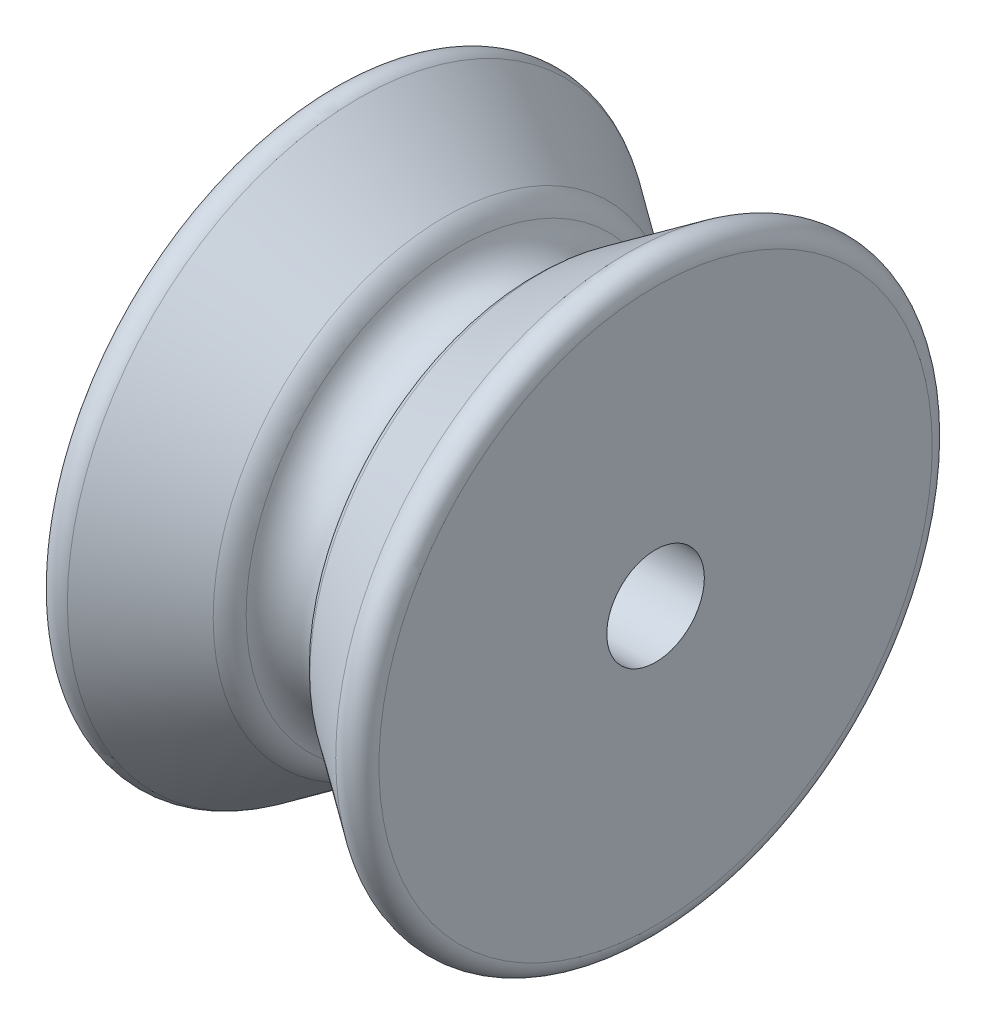
SolidWorks part; units mm, degrees
ref_plane "Front Plane" through (0, 0, 0) normal (0, 0, 1) x (1, 0, 0)
ref_plane "Top Plane" through (0, 0, 0) normal (0, 1, 0) x (1, 0, 0)
ref_plane "Right Plane" through (0, 0, 0) normal (1, 0, 0) x (0, 0, -1)
sketch "Sketch1" plane through (0, 0, 0) normal (1, 0, 0) x (0, 0, -1)
  circle A0 centre (0, 0) radius 20
  dimension "D1" = 40
extrude "Boss-Extrude1" add sketch "Sketch1" along normal blind 18
sketch "Sketch2" plane through (18, 0, 0) normal (1, 0, 0) x (0, 0, -1)
  circle A0 centre (0, 0) radius 2.7
  dimension "D1" = 5.4
extrude "Cut-Extrude1" cut sketch "Sketch2" against normal blind 18
sketch "Sketch3" plane through (0, 0, 0) normal (0, 0, 1) x (1, 0, 0)
  line L0 (0, 0) -> (18, 0) construction
  line L1 (18, -20) -> (18, 20) construction
  line L2 (9, 0) -> (9, 12.3325) construction
  line L3 (7, 12.3325) -> (11, 12.3325) construction
  line L4 (11, 12.3325) -> (27.0916, 23.6)
  line L5 (7, 12.3325) -> (-9.0916, 23.6)
  line L6 (-9.0916, 23.6) -> (27.0916, 23.6)
  line L7 (9, 12.3325) -> (9, 14.5328) construction
  line L8 (18, 20) -> (0, 20) construction
  arc A0 (7, 12.3325) -> (11, 12.3325) centre (9, 15.1888) ccw construction
  arc A1 (11, 12.3325) -> (7, 12.3325) centre (9, 12.3325) cw
  point P10 (9, 12.3325)
  point P17 (9, 23.6)
  point P18 (0, 0)
  point P19 (0, 0)
  dimension "D1" = 4
  dimension "D2" = 110
ref_axis "Axis1" through (0, 0, 0) along (1, 0, 0)
revolve "Cut-Revolve1" cut sketch "Sketch3" angle 360 about L0
fillet "Fillet1" radius 1 2 edges at (0, 0, -17.234) (18, 0, -17.234)
fillet "Fillet2" radius 2 2 edges at (7, 0, 12.3325) (11, 0, 12.3325)
